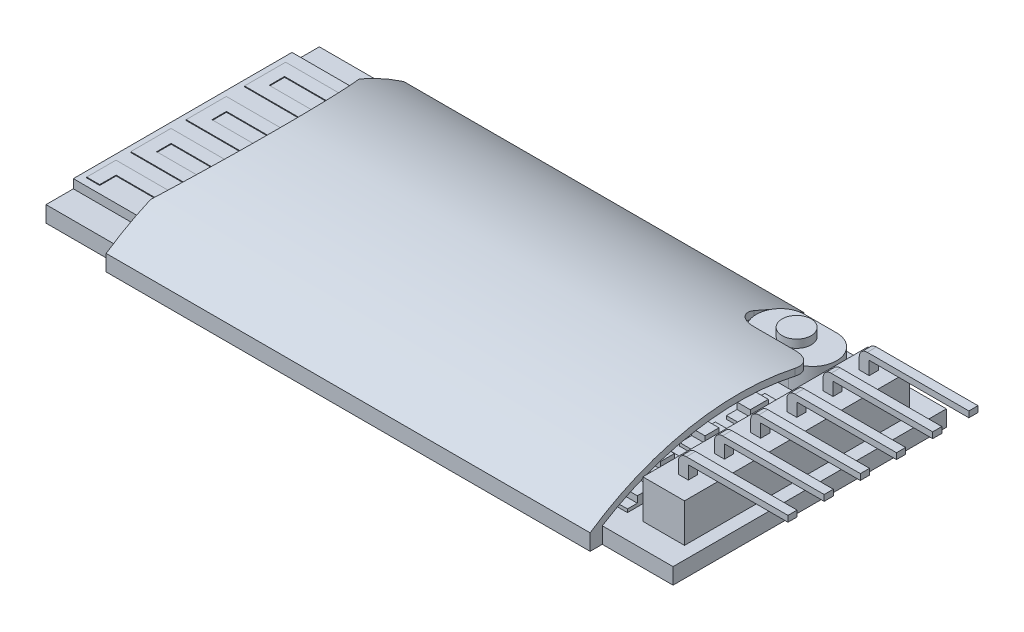
SolidWorks part; units mm, degrees
ref_plane "前视基准面" through (0, 0, 0) normal (0, 0, 1) x (1, 0, 0)
ref_plane "上视基准面" through (0, 0, 0) normal (0, 1, 0) x (1, 0, 0)
ref_plane "右视基准面" through (0, 0, 0) normal (1, 0, 0) x (0, 0, -1)
sketch "草图1" plane through (0, 0, 0) normal (0, 1, 0) x (1, 0, 0)
  line L1 (-19.5, 8.5) -> (19.5, 8.5)
  line L2 (-19.5, 8.5) -> (-19.5, -8.5)
  line L3 (-19.5, -8.5) -> (19.5, -8.5)
  line L4 (19.5, 8.5) -> (19.5, -8.5)
  line L5 (-19.5, 8.5) -> (19.5, -8.5) construction
  line L6 (-19.5, -8.5) -> (19.5, 8.5) construction
  point P0 (0, 0)
  dimension "D1" = 39
  dimension "D2" = 17
extrude "凸台-拉伸1" add sketch "草图1" along normal blind 1
sketch "草图2" plane through (0, 1, 0) normal (0, 1, 0) x (1, 0, 0)
  line L0 (-19.5, 8.5) -> (-19.5, -8.5) construction
  line L1 (-19.5, 6.8) -> (9.5, 6.8)
  line L2 (-19.5, 6.8) -> (-19.5, -6.8)
  line L3 (-19.5, -6.8) -> (9.5, -6.8)
  line L4 (9.5, 6.8) -> (9.5, -6.8)
  line L5 (-19.5, 6.8) -> (9.5, -6.8) construction
  line L6 (-19.5, -6.8) -> (9.5, 6.8) construction
  line L7 (19.5, 8.5) -> (-19.5, 8.5) construction
  line L8 (-19.5, -8.5) -> (19.5, -8.5) construction
  point P4 (-5, 0)
  dimension "D1" = 1.7
  dimension "D2" = 29
  dimension "D3" = 1.7
extrude "凸台-拉伸2" add sketch "草图2" along normal blind 0.5
sketch "草图3" plane through (0, 1.5, 0) normal (0, 1, 0) x (1, 0, 0)
  line L0 (-13.945, 4.2678) -> (-13.945, 1.5334)
  line L1 (-19.1193, 6.0235) -> (-13.945, 6.0235)
  line L2 (-19.1193, 6.0235) -> (-19.1193, 3.4678)
  line L3 (-19.1193, -6.3499) -> (-18.3103, -6.3499)
  line L5 (-19.1193, 6.0235) -> (-13.945, -6.3499) construction
  line L6 (-19.1193, -6.3499) -> (-13.945, 6.0235) construction
  line L7 (-13.945, 5.2235) -> (-18.3851, 5.2235)
  line L9 (-13.945, 4.2678) -> (-18.3851, 4.2678)
  line L10 (-18.3851, 5.2235) -> (-18.3851, 4.2678)
  line L11 (-13.945, 5.2235) -> (-18.3851, 4.2678) construction
  line L12 (-13.945, 4.2678) -> (-18.3851, 5.2235) construction
  line L13 (-19.1193, 3.4678) -> (-14.681, 3.4678)
  line L15 (-19.1193, 2.3334) -> (-14.681, 2.3334)
  line L16 (-14.681, 3.4678) -> (-14.681, 2.3334)
  line L17 (-19.1193, 3.4678) -> (-14.681, 2.3334) construction
  line L18 (-19.1193, 2.3334) -> (-14.681, 3.4678) construction
  line L19 (-13.945, 1.5334) -> (-18.3103, 1.5334)
  line L21 (-13.945, 0.6368) -> (-18.3103, 0.6368)
  line L22 (-18.3103, 1.5334) -> (-18.3103, 0.6368)
  line L23 (-13.945, 1.5334) -> (-18.3103, 0.6368) construction
  line L24 (-13.945, 0.6368) -> (-18.3103, 1.5334) construction
  line L25 (-19.1193, -0.1632) -> (-14.6759, -0.1632)
  line L27 (-19.1193, -1.1073) -> (-14.6759, -1.1073)
  line L28 (-14.6759, -0.1632) -> (-14.6759, -1.1073)
  line L29 (-19.1193, -0.1632) -> (-14.6759, -1.1073) construction
  line L30 (-19.1193, -1.1073) -> (-14.6759, -0.1632) construction
  line L31 (-13.945, -1.9073) -> (-18.3103, -1.9073)
  line L33 (-13.945, -2.809) -> (-18.3103, -2.809)
  line L34 (-18.3103, -1.9073) -> (-18.3103, -2.809)
  line L35 (-13.945, -1.9073) -> (-18.3103, -2.809) construction
  line L36 (-13.945, -2.809) -> (-18.3103, -1.9073) construction
  line L37 (-19.1193, -3.609) -> (-14.7067, -3.609)
  line L39 (-19.1193, -4.5285) -> (-14.7067, -4.5285)
  line L40 (-14.7067, -3.609) -> (-14.7067, -4.5285)
  line L41 (-19.1193, -3.609) -> (-14.7067, -4.5285) construction
  line L42 (-19.1193, -4.5285) -> (-14.7067, -3.609) construction
  line L43 (-13.945, -5.3285) -> (-18.3103, -5.3285)
  line L46 (-18.3103, -5.3285) -> (-18.3103, -6.3499)
  line L47 (-13.945, -5.3285) -> (-18.3103, -6.3499) construction
  line L48 (-13.945, -6.3499) -> (-18.3103, -5.3285) construction
  line L49 (-19.1193, 2.3334) -> (-19.1193, -0.1632)
  line L50 (-13.945, 0.6368) -> (-13.945, -1.9073)
  line L51 (-19.1193, -1.1073) -> (-19.1193, -3.609)
  line L52 (-13.945, -2.809) -> (-13.945, -5.3285)
  line L53 (-19.1193, -4.5285) -> (-19.1193, -6.3499)
  line L55 (-13.945, 6.0235) -> (-12.645, 6.0235)
  line L57 (-13.945, 5.2235) -> (-12.645, 5.2235)
  line L58 (-12.645, 6.0235) -> (-12.645, 5.2235)
  line L59 (-13.945, 6.0235) -> (-12.645, 5.2235) construction
  line L60 (-13.945, 5.2235) -> (-12.645, 6.0235) construction
  point P4 (-16.5322, -0.1632)
  point P9 (-16.1651, 4.7457)
  point P14 (-16.9002, 2.9006)
  point P19 (-16.1277, 1.0851)
  point P24 (-16.8976, -0.6352)
  point P29 (-16.1277, -2.3581)
  point P34 (-16.913, -4.0688)
  point P38 (-16.1277, -5.8392)
  point P41 (-13.295, 5.6235)
  dimension "D1" = 0.8
  dimension "D2" = 0.8
  dimension "D3" = 0.8
  dimension "D4" = 0.8
  dimension "D5" = 0.8
  dimension "D6" = 0.8
  dimension "D7" = 0.8
  dimension "D8" = 1.3
extrude "凸台-拉伸3" add sketch "草图3" along normal blind 0.1
sketch "草图4" plane through (0, 1.5, 0) normal (0, 1, 0) x (1, 0, 0)
  line L0 (-19.5, -6.8) -> (9.5, -6.8) construction
  line L1 (-19.5, 6.8) -> (-12.645, 6.8)
  line L2 (-19.5, 6.8) -> (-19.5, -6.8)
  line L3 (-19.5, -6.8) -> (-12.645, -6.8)
  line L4 (-12.645, 6.8) -> (-12.645, -6.8)
  line L5 (-19.5, 6.8) -> (-12.645, -6.8) construction
  line L6 (-19.5, -6.8) -> (-12.645, 6.8) construction
  line L7 (-12.645, 5.2235) -> (-12.645, 6.0235) construction
  point P4 (-16.0725, 0)
  dimension "D1" = 0
extrude "凸台-拉伸4" add sketch "草图4" along normal blind 0.05
sketch "草图5" plane through (0, 1.5, 0) normal (0, 1, 0) x (1, 0, 0)
  line L0 (-12.645, 0) -> (13.1235, 0) construction
  line L1 (-12.645, -6.8) -> (-12.645, 6.8) construction
  line L2 (-12.645, -6.8) -> (9.5, -6.8) construction
  line L3 (9.5, -6.8) -> (9.5, 6.8) construction
  circle A0 centre (-11.3889, -6.8) radius 0.5
  circle A1 centre (-9.2689, -6.8) radius 0.5
  circle A2 centre (-7.1489, -6.8) radius 0.5
  circle A3 centre (-5.0289, -6.8) radius 0.5
  circle A4 centre (-2.9089, -6.8) radius 0.5
  circle A5 centre (-0.7889, -6.8) radius 0.5
  circle A6 centre (1.3311, -6.8) radius 0.5
  circle A7 centre (3.4511, -6.8) radius 0.5
  circle A8 centre (5.5711, -6.8) radius 0.5
  circle A9 centre (7.6911, -6.8) radius 0.5
  circle A10 centre (7.6911, 6.8) radius 0.5
  circle A11 centre (5.5711, 6.8) radius 0.5
  circle A12 centre (3.4511, 6.8) radius 0.5
  circle A13 centre (1.3311, 6.8) radius 0.5
  circle A14 centre (-0.7889, 6.8) radius 0.5
  circle A15 centre (-2.9089, 6.8) radius 0.5
  circle A16 centre (-5.0289, 6.8) radius 0.5
  circle A17 centre (-7.1489, 6.8) radius 0.5
  circle A18 centre (-9.2689, 6.8) radius 0.5
  circle A19 centre (-11.3889, 6.8) radius 0.5
  circle A20 centre (9.5, 5.7827) radius 0.5
  circle A21 centre (9.5, 4.1327) radius 0.5
  circle A22 centre (9.5, 2.4827) radius 0.5
  circle A23 centre (9.5, 0.8327) radius 0.5
  circle A24 centre (9.5, -0.8173) radius 0.5
  circle A25 centre (9.5, -2.4673) radius 0.5
  circle A26 centre (9.5, -4.1173) radius 0.5
  circle A27 centre (9.5, -5.7673) radius 0.5
  dimension "D2" = 1
  dimension "D3" = 1
  dimension "D1" = 10
  dimension "D4" = 8
extrude "切除-拉伸1" cut sketch "草图5" against normal up to surface (0.5 mm away) up to face at (-2.5, 1, 0)
sketch "草图6" plane through (0, 1.5, 0) normal (0, 1, 0) x (1, 0, 0)
  line L0 (-11.8889, 6.8) -> (-19.5, 6.8) construction
  line L1 (-11.9389, 6.8) -> (-11.8889, 6.8)
  line L2 (-11.9389, 6.8) -> (-11.9389, 6.2)
  line L3 (-11.9389, 6.2) -> (-10.8389, 6.2)
  line L4 (-10.8389, 6.8) -> (-10.8389, 6.2)
  line L5 (-11.9389, 6.8) -> (-10.8389, 6.2) construction
  line L6 (-11.9389, 6.2) -> (-10.8389, 6.8) construction
  line L7 (-10.8889, 6.8) -> (-10.8389, 6.8)
  line L8 (-12.645, 0) -> (11.007, 0) construction
  line L9 (-12.645, -6.8) -> (-12.645, 6.8) construction
  line L10 (-9.8189, 6.8) -> (-9.7689, 6.8)
  line L11 (-9.8189, 6.8) -> (-9.8189, 6.2)
  line L12 (-9.8189, 6.2) -> (-8.7189, 6.2)
  line L13 (-8.7189, 6.8) -> (-8.7189, 6.2)
  line L14 (-8.7689, 6.8) -> (-8.7189, 6.8)
  line L15 (-7.6989, 6.8) -> (-7.6489, 6.8)
  line L16 (-7.6989, 6.8) -> (-7.6989, 6.2)
  line L17 (-7.6989, 6.2) -> (-6.5989, 6.2)
  line L18 (-6.5989, 6.8) -> (-6.5989, 6.2)
  line L19 (-6.6489, 6.8) -> (-6.5989, 6.8)
  line L20 (-5.5789, 6.8) -> (-5.5289, 6.8)
  line L21 (-5.5789, 6.8) -> (-5.5789, 6.2)
  line L22 (-5.5789, 6.2) -> (-4.4789, 6.2)
  line L23 (-4.4789, 6.8) -> (-4.4789, 6.2)
  line L24 (-4.5289, 6.8) -> (-4.4789, 6.8)
  line L25 (-3.4589, 6.8) -> (-3.4089, 6.8)
  line L26 (-3.4589, 6.8) -> (-3.4589, 6.2)
  line L27 (-3.4589, 6.2) -> (-2.3589, 6.2)
  line L28 (-2.3589, 6.8) -> (-2.3589, 6.2)
  line L29 (-2.4089, 6.8) -> (-2.3589, 6.8)
  line L30 (-1.3389, 6.8) -> (-1.2889, 6.8)
  line L31 (-1.3389, 6.8) -> (-1.3389, 6.2)
  line L32 (-1.3389, 6.2) -> (-0.2389, 6.2)
  line L33 (-0.2389, 6.8) -> (-0.2389, 6.2)
  line L34 (-0.2889, 6.8) -> (-0.2389, 6.8)
  line L35 (0.7811, 6.8) -> (0.8311, 6.8)
  line L36 (0.7811, 6.8) -> (0.7811, 6.2)
  line L37 (0.7811, 6.2) -> (1.8811, 6.2)
  line L38 (1.8811, 6.8) -> (1.8811, 6.2)
  line L39 (1.8311, 6.8) -> (1.8811, 6.8)
  line L40 (2.9011, 6.8) -> (2.9511, 6.8)
  line L41 (2.9011, 6.8) -> (2.9011, 6.2)
  line L42 (2.9011, 6.2) -> (4.0011, 6.2)
  line L43 (4.0011, 6.8) -> (4.0011, 6.2)
  line L44 (3.9511, 6.8) -> (4.0011, 6.8)
  line L45 (5.0211, 6.8) -> (5.0711, 6.8)
  line L46 (5.0211, 6.8) -> (5.0211, 6.2)
  line L47 (5.0211, 6.2) -> (6.1211, 6.2)
  line L48 (6.1211, 6.8) -> (6.1211, 6.2)
  line L49 (6.0711, 6.8) -> (6.1211, 6.8)
  line L50 (7.1411, 6.8) -> (7.1911, 6.8)
  line L51 (7.1411, 6.8) -> (7.1411, 6.2)
  line L52 (7.1411, 6.2) -> (8.2411, 6.2)
  line L53 (8.2411, 6.8) -> (8.2411, 6.2)
  line L54 (8.1911, 6.8) -> (8.2411, 6.8)
  line L55 (-9.7689, 6.8) -> (-10.8889, 6.8) construction
  line L56 (9.5, 6.2827) -> (9.5, 6.8) construction
  line L57 (9.5, 6.3327) -> (8.9, 6.3327)
  line L58 (9.5, 6.3327) -> (9.5, 6.2827)
  line L59 (9.5, 5.2327) -> (8.9, 5.2327)
  line L60 (8.9, 6.3327) -> (8.9, 5.2327)
  line L61 (9.5, 6.3327) -> (8.9, 5.2327) construction
  line L62 (9.5, 5.2327) -> (8.9, 6.3327) construction
  line L63 (9.5, 5.2827) -> (9.5, 5.2327)
  line L64 (8.9, 4.6827) -> (8.9, 3.5827)
  line L65 (9.5, 4.6827) -> (8.9, 4.6827)
  line L66 (9.5, 3.5827) -> (8.9, 3.5827)
  line L67 (8.9, 3.0327) -> (8.9, 1.9327)
  line L68 (9.5, 3.0327) -> (8.9, 3.0327)
  line L69 (9.5, 1.9327) -> (8.9, 1.9327)
  line L70 (8.9, 1.3827) -> (8.9, 0.2827)
  line L71 (9.5, 1.3827) -> (8.9, 1.3827)
  line L72 (9.5, 0.2827) -> (8.9, 0.2827)
  line L73 (8.9, -0.2673) -> (8.9, -1.3673)
  line L74 (9.5, -0.2673) -> (8.9, -0.2673)
  line L75 (9.5, -1.3673) -> (8.9, -1.3673)
  line L76 (8.9, -1.9173) -> (8.9, -3.0173)
  line L77 (9.5, -1.9173) -> (8.9, -1.9173)
  line L78 (9.5, -3.0173) -> (8.9, -3.0173)
  line L79 (8.9, -3.5673) -> (8.9, -4.6673)
  line L80 (9.5, -3.5673) -> (8.9, -3.5673)
  line L81 (9.5, -4.6673) -> (8.9, -4.6673)
  line L82 (8.9, -5.2173) -> (8.9, -6.3173)
  line L83 (9.5, -5.2173) -> (8.9, -5.2173)
  line L84 (9.5, -6.3173) -> (8.9, -6.3173)
  line L85 (9.5, 1.9827) -> (9.5, 1.9327)
  line L86 (-11.9389, -6.2) -> (-10.8389, -6.8) construction
  line L87 (-11.9389, -6.8) -> (-10.8389, -6.2) construction
  line L88 (8.1911, -6.8) -> (8.2411, -6.8)
  line L89 (8.2411, -6.8) -> (8.2411, -6.2)
  line L90 (7.1411, -6.2) -> (8.2411, -6.2)
  line L91 (7.1411, -6.8) -> (7.1411, -6.2)
  line L92 (7.1411, -6.8) -> (7.1911, -6.8)
  line L93 (6.0711, -6.8) -> (6.1211, -6.8)
  line L94 (6.1211, -6.8) -> (6.1211, -6.2)
  line L95 (5.0211, -6.2) -> (6.1211, -6.2)
  line L96 (5.0211, -6.8) -> (5.0211, -6.2)
  line L97 (5.0211, -6.8) -> (5.0711, -6.8)
  line L98 (3.9511, -6.8) -> (4.0011, -6.8)
  line L99 (4.0011, -6.8) -> (4.0011, -6.2)
  line L100 (2.9011, -6.2) -> (4.0011, -6.2)
  line L101 (2.9011, -6.8) -> (2.9011, -6.2)
  line L102 (2.9011, -6.8) -> (2.9511, -6.8)
  line L103 (1.8311, -6.8) -> (1.8811, -6.8)
  line L104 (1.8811, -6.8) -> (1.8811, -6.2)
  line L105 (0.7811, -6.2) -> (1.8811, -6.2)
  line L106 (0.7811, -6.8) -> (0.7811, -6.2)
  line L107 (0.7811, -6.8) -> (0.8311, -6.8)
  line L108 (-0.2889, -6.8) -> (-0.2389, -6.8)
  line L109 (-0.2389, -6.8) -> (-0.2389, -6.2)
  line L110 (-1.3389, -6.2) -> (-0.2389, -6.2)
  line L111 (-1.3389, -6.8) -> (-1.3389, -6.2)
  line L112 (-1.3389, -6.8) -> (-1.2889, -6.8)
  line L113 (-2.4089, -6.8) -> (-2.3589, -6.8)
  line L114 (-2.3589, -6.8) -> (-2.3589, -6.2)
  line L115 (-3.4589, -6.2) -> (-2.3589, -6.2)
  line L116 (-3.4589, -6.8) -> (-3.4589, -6.2)
  line L117 (-3.4589, -6.8) -> (-3.4089, -6.8)
  line L118 (-4.5289, -6.8) -> (-4.4789, -6.8)
  line L119 (-4.4789, -6.8) -> (-4.4789, -6.2)
  line L120 (-5.5789, -6.2) -> (-4.4789, -6.2)
  line L121 (-5.5789, -6.8) -> (-5.5789, -6.2)
  line L122 (-5.5789, -6.8) -> (-5.5289, -6.8)
  line L123 (-6.6489, -6.8) -> (-6.5989, -6.8)
  line L124 (-6.5989, -6.8) -> (-6.5989, -6.2)
  line L125 (-7.6989, -6.2) -> (-6.5989, -6.2)
  line L126 (-7.6989, -6.8) -> (-7.6989, -6.2)
  line L127 (-7.6989, -6.8) -> (-7.6489, -6.8)
  line L128 (-8.7689, -6.8) -> (-8.7189, -6.8)
  line L129 (-8.7189, -6.8) -> (-8.7189, -6.2)
  line L130 (-9.8189, -6.2) -> (-8.7189, -6.2)
  line L131 (-9.8189, -6.8) -> (-9.8189, -6.2)
  line L132 (-9.8189, -6.8) -> (-9.7689, -6.8)
  line L133 (-10.8889, -6.8) -> (-10.8389, -6.8)
  line L134 (-10.8389, -6.8) -> (-10.8389, -6.2)
  line L135 (-11.9389, -6.2) -> (-10.8389, -6.2)
  line L136 (-11.9389, -6.8) -> (-11.9389, -6.2)
  line L137 (-11.9389, -6.8) -> (-11.8889, -6.8)
  line L138 (9.5, 4.6827) -> (9.5, 4.6327)
  line L139 (9.5, 3.6327) -> (9.5, 3.5827)
  line L140 (9.5, 3.0327) -> (9.5, 2.9827)
  line L141 (9.5, 1.3827) -> (9.5, 1.3327)
  line L142 (9.5, 0.3327) -> (9.5, 0.2827)
  line L143 (9.5, -0.2673) -> (9.5, -0.3173)
  line L144 (9.5, -1.3673) -> (9.5, -1.3173)
  line L145 (9.5, -1.9173) -> (9.5, -1.9673)
  line L146 (9.5, -2.9673) -> (9.5, -3.0173)
  line L147 (9.5, -3.5673) -> (9.5, -3.6173)
  line L148 (9.5, -4.6173) -> (9.5, -4.6673)
  line L149 (9.5, -5.2173) -> (9.5, -5.2673)
  line L150 (9.5, -6.2673) -> (9.5, -6.3173)
  arc A0 (-11.8889, 6.8) -> (-10.8889, 6.8) centre (-11.3889, 6.8) ccw
  arc A1 (-9.7689, 6.8) -> (-8.7689, 6.8) centre (-9.2689, 6.8) ccw
  arc A2 (-7.6489, 6.8) -> (-6.6489, 6.8) centre (-7.1489, 6.8) ccw
  arc A3 (-5.5289, 6.8) -> (-4.5289, 6.8) centre (-5.0289, 6.8) ccw
  arc A4 (-3.4089, 6.8) -> (-2.4089, 6.8) centre (-2.9089, 6.8) ccw
  arc A5 (-1.2889, 6.8) -> (-0.2889, 6.8) centre (-0.7889, 6.8) ccw
  arc A6 (0.8311, 6.8) -> (1.8311, 6.8) centre (1.3311, 6.8) ccw
  arc A7 (2.9511, 6.8) -> (3.9511, 6.8) centre (3.4511, 6.8) ccw
  arc A8 (5.0711, 6.8) -> (6.0711, 6.8) centre (5.5711, 6.8) ccw
  arc A9 (7.1911, 6.8) -> (8.1911, 6.8) centre (7.6911, 6.8) ccw
  arc A10 (9.5, 6.2827) -> (9.5, 5.2827) centre (9.5, 5.7827) ccw
  arc A11 (9.5, 4.6327) -> (9.5, 3.6327) centre (9.5, 4.1327) ccw
  arc A12 (9.5, 2.9827) -> (9.5, 1.9827) centre (9.5, 2.4827) ccw
  arc A13 (9.5, 1.3327) -> (9.5, 0.3327) centre (9.5, 0.8327) ccw
  arc A14 (9.5, -0.3173) -> (9.5, -1.3173) centre (9.5, -0.8173) ccw
  arc A15 (9.5, -1.9673) -> (9.5, -2.9673) centre (9.5, -2.4673) ccw
  arc A16 (9.5, -3.6173) -> (9.5, -4.6173) centre (9.5, -4.1173) ccw
  arc A17 (9.5, -5.2673) -> (9.5, -6.2673) centre (9.5, -5.7673) ccw
  arc A18 (7.1911, -6.8) -> (8.1911, -6.8) centre (7.6911, -6.8) cw
  arc A19 (5.0711, -6.8) -> (6.0711, -6.8) centre (5.5711, -6.8) cw
  arc A20 (2.9511, -6.8) -> (3.9511, -6.8) centre (3.4511, -6.8) cw
  arc A21 (0.8311, -6.8) -> (1.8311, -6.8) centre (1.3311, -6.8) cw
  arc A22 (-1.2889, -6.8) -> (-0.2889, -6.8) centre (-0.7889, -6.8) cw
  arc A23 (-3.4089, -6.8) -> (-2.4089, -6.8) centre (-2.9089, -6.8) cw
  arc A24 (-5.5289, -6.8) -> (-4.5289, -6.8) centre (-5.0289, -6.8) cw
  arc A25 (-7.6489, -6.8) -> (-6.6489, -6.8) centre (-7.1489, -6.8) cw
  arc A26 (-9.7689, -6.8) -> (-8.7689, -6.8) centre (-9.2689, -6.8) cw
  arc A27 (-11.8889, -6.8) -> (-10.8889, -6.8) centre (-11.3889, -6.8) cw
  point P4 (-11.3889, 6.5)
  point P85 (9.2, 5.7827)
  point P213 (-11.3889, -6.5)
  dimension "D2" = 1.1
  dimension "D3" = 0.55
  dimension "D4" = 0.6
  dimension "D5" = 1.1
  dimension "D6" = 0.55
  dimension "D7" = 0.6
  dimension "D1" = 10
  dimension "D8" = 8
extrude "凸台-拉伸5" add sketch "草图6" along normal blind 0.05
sketch "草图9" plane through (0, 1.5, 0) normal (0, 1, 0) x (1, 0, 0)
  line L1 (-6.7387, 5.1688) -> (0.5298, 5.1688)
  line L2 (-6.7387, 5.1688) -> (-6.7387, -2.1492)
  line L3 (-6.7387, -2.1492) -> (0.5298, -2.1492)
  line L4 (0.5298, 5.1688) -> (0.5298, -2.1492)
  line L5 (-6.7387, 5.1688) -> (0.5298, -2.1492) construction
  line L6 (-6.7387, -2.1492) -> (0.5298, 5.1688) construction
  line L7 (2.1614, 5.1688) -> (8.0685, 5.1688)
  line L8 (2.1614, 5.1688) -> (2.1614, -3.3971)
  line L9 (2.1614, -3.3971) -> (8.0685, -3.3971)
  line L10 (8.0685, 5.1688) -> (8.0685, -3.3971)
  line L11 (2.1614, 5.1688) -> (8.0685, -3.3971) construction
  line L12 (2.1614, -3.3971) -> (8.0685, 5.1688) construction
  point P4 (-3.1045, 1.5098)
  point P9 (5.1149, 0.8859)
extrude "凸台-拉伸6" add sketch "草图9" along normal blind 0.8
sketch "草图10" plane through (0, 1.5, 0) normal (0, 1, 0) x (1, 0, 0)
  line L1 (-7.8532, 5.0672) -> (-7.2835, 5.0672)
  line L2 (-7.8532, 5.0672) -> (-7.8532, 3.0054)
  line L3 (-7.8532, 3.0054) -> (-7.2835, 3.0054)
  line L4 (-7.2835, 5.0672) -> (-7.2835, 3.0054)
  line L5 (-7.8532, 5.0672) -> (-7.2835, 3.0054) construction
  line L6 (-7.8532, 3.0054) -> (-7.2835, 5.0672) construction
  line L7 (-12.0311, 5.0672) -> (-11.2444, 5.0672)
  line L8 (-12.0311, 5.0672) -> (-12.0311, 3.331)
  line L9 (-12.0311, 3.331) -> (-11.2444, 3.331)
  line L10 (-11.2444, 5.0672) -> (-11.2444, 3.331)
  line L11 (-12.0311, 5.0672) -> (-11.2444, 3.331) construction
  line L12 (-12.0311, 3.331) -> (-11.2444, 5.0672) construction
  line L13 (-10.8374, 5.0672) -> (-10.1211, 5.0672)
  line L14 (-10.8374, 5.0672) -> (-10.8374, 3.331)
  line L15 (-10.8374, 3.331) -> (-10.1211, 3.331)
  line L16 (-10.1211, 5.0672) -> (-10.1211, 3.331)
  line L17 (-10.8374, 5.0672) -> (-10.1211, 3.331) construction
  line L18 (-10.8374, 3.331) -> (-10.1211, 5.0672) construction
  line L19 (-8.7485, -1.4709) -> (-7.2835, -1.4709)
  line L20 (-8.7485, -1.4709) -> (-8.7485, -2.1492)
  line L21 (-8.7485, -2.1492) -> (-7.2835, -2.1492)
  line L22 (-7.2835, -1.4709) -> (-7.2835, -2.1492)
  line L23 (-8.7485, -1.4709) -> (-7.2835, -2.1492) construction
  line L24 (-8.7485, -2.1492) -> (-7.2835, -1.4709) construction
  line L25 (-11.6377, -1.4709) -> (-10.8374, -1.4709)
  line L26 (-11.6377, -1.4709) -> (-11.6377, -3.4785)
  line L27 (-11.6377, -3.4785) -> (-10.8374, -3.4785)
  line L28 (-10.8374, -1.4709) -> (-10.8374, -3.4785)
  line L29 (-11.6377, -1.4709) -> (-10.8374, -3.4785) construction
  line L30 (-11.6377, -3.4785) -> (-10.8374, -1.4709) construction
  line L31 (-10.4792, -1.4709) -> (-9.6437, -1.4709)
  line L32 (-10.4792, -1.4709) -> (-10.4792, -3.4738)
  line L33 (-10.4792, -3.4738) -> (-9.6437, -3.4738)
  line L34 (-9.6437, -1.4709) -> (-9.6437, -3.4738)
  line L35 (-10.4792, -1.4709) -> (-9.6437, -3.4738) construction
  line L36 (-10.4792, -3.4738) -> (-9.6437, -1.4709) construction
  line L37 (-12.1459, -3.815) -> (-9.6437, -3.815)
  line L38 (-12.1459, -3.815) -> (-12.1459, -4.451)
  line L39 (-12.1459, -4.451) -> (-9.6437, -4.451)
  line L40 (-9.6437, -3.815) -> (-9.6437, -4.451)
  line L41 (-12.1459, -3.815) -> (-9.6437, -4.451) construction
  line L42 (-12.1459, -4.451) -> (-9.6437, -3.815) construction
  line L43 (-8.7485, -2.9774) -> (-7.8532, -2.9774)
  line L44 (-8.7485, -2.9774) -> (-8.7485, -5.3352)
  line L45 (-8.7485, -5.3352) -> (-7.8532, -5.3352)
  line L46 (-7.8532, -2.9774) -> (-7.8532, -5.3352)
  line L47 (-8.7485, -2.9774) -> (-7.8532, -5.3352) construction
  line L48 (-8.7485, -5.3352) -> (-7.8532, -2.9774) construction
  line L49 (-7.2835, -2.6671) -> (-6.8718, -2.6671)
  line L50 (-7.2835, -2.6671) -> (-7.2835, -3.2411)
  line L51 (-7.2835, -3.2411) -> (-6.8718, -3.2411)
  line L52 (-6.8718, -2.6671) -> (-6.8718, -3.2411)
  line L53 (-7.2835, -2.6671) -> (-6.8718, -3.2411) construction
  line L54 (-7.2835, -3.2411) -> (-6.8718, -2.6671) construction
  line L55 (-7.2835, -3.5364) -> (-6.8718, -3.5364)
  line L56 (-7.2835, -3.5364) -> (-7.2835, -4.133)
  line L57 (-7.2835, -4.133) -> (-6.8718, -4.133)
  line L58 (-6.8718, -3.5364) -> (-6.8718, -4.133)
  line L59 (-7.2835, -3.5364) -> (-6.8718, -4.133) construction
  line L60 (-7.2835, -4.133) -> (-6.8718, -3.5364) construction
  line L61 (-7.2835, -4.451) -> (-6.577, -4.451)
  line L62 (-7.2835, -4.451) -> (-7.2835, -5.1801)
  line L63 (-7.2835, -5.1801) -> (-6.577, -5.1801)
  line L64 (-6.577, -4.451) -> (-6.577, -5.1801)
  line L65 (-7.2835, -4.451) -> (-6.577, -5.1801) construction
  line L66 (-7.2835, -5.1801) -> (-6.577, -4.451) construction
  line L67 (0.8726, 4.8427) -> (1.6485, 4.8427)
  line L68 (0.8726, 4.8427) -> (0.8726, 2.6274)
  line L69 (0.8726, 2.6274) -> (1.6485, 2.6274)
  line L70 (1.6485, 4.8427) -> (1.6485, 2.6274)
  line L71 (0.8726, 4.8427) -> (1.6485, 2.6274) construction
  line L72 (0.8726, 2.6274) -> (1.6485, 4.8427) construction
  line L73 (0.8726, 2.0919) -> (1.6485, 2.0919)
  line L74 (0.8726, 2.0919) -> (0.8726, 0)
  line L75 (0.8726, 0) -> (1.6485, 0)
  line L76 (1.6485, 2.0919) -> (1.6485, 0)
  line L77 (0.8726, 2.0919) -> (1.6485, 0) construction
  line L78 (0.8726, 0) -> (1.6485, 2.0919) construction
  line L79 (0.8726, -0.4423) -> (1.6485, -0.4423)
  line L80 (0.8726, -0.4423) -> (0.8726, -2.6456)
  line L81 (0.8726, -2.6456) -> (1.6485, -2.6456)
  line L82 (1.6485, -0.4423) -> (1.6485, -2.6456)
  line L83 (0.8726, -0.4423) -> (1.6485, -2.6456) construction
  line L84 (0.8726, -2.6456) -> (1.6485, -0.4423) construction
  line L85 (3.574, -3.8347) -> (4.3685, -3.8347)
  line L86 (3.574, -3.8347) -> (3.574, -5.7088)
  line L87 (3.574, -5.7088) -> (4.3685, -5.7088)
  line L88 (4.3685, -3.8347) -> (4.3685, -5.7088)
  line L89 (3.574, -3.8347) -> (4.3685, -5.7088) construction
  line L90 (3.574, -5.7088) -> (4.3685, -3.8347) construction
  line L91 (4.9088, -3.8347) -> (5.6716, -3.8347)
  line L92 (4.9088, -3.8347) -> (4.9088, -5.7088)
  line L93 (4.9088, -5.7088) -> (5.6716, -5.7088)
  line L94 (5.6716, -3.8347) -> (5.6716, -5.7088)
  line L95 (4.9088, -3.8347) -> (5.6716, -5.7088) construction
  line L96 (4.9088, -5.7088) -> (5.6716, -3.8347) construction
  line L97 (6.1815, -3.8347) -> (7.0064, -3.8347)
  line L98 (6.1815, -3.8347) -> (6.1815, -5.7088)
  line L99 (6.1815, -5.7088) -> (7.0064, -5.7088)
  line L100 (7.0064, -3.8347) -> (7.0064, -5.7088)
  line L101 (6.1815, -3.8347) -> (7.0064, -5.7088) construction
  line L102 (6.1815, -5.7088) -> (7.0064, -3.8347) construction
  line L103 (7.5926, -3.8347) -> (8.2777, -3.8347)
  line L104 (7.5926, -3.8347) -> (7.5926, -5.7088)
  line L105 (7.5926, -5.7088) -> (8.2777, -5.7088)
  line L106 (8.2777, -3.8347) -> (8.2777, -5.7088)
  line L107 (7.5926, -3.8347) -> (8.2777, -5.7088) construction
  line L108 (7.5926, -5.7088) -> (8.2777, -3.8347) construction
  line L113 (-6.2012, -3.1428) -> (-3.3741, -5.0092) construction
  line L114 (-6.2012, -5.0092) -> (-3.3741, -3.1428) construction
  line L115 (-3.1413, -2.6671) -> (-2.6763, -2.6671)
  line L116 (-3.1413, -2.6671) -> (-3.1413, -5.3352)
  line L117 (-3.1413, -5.3352) -> (-2.6763, -5.3352)
  line L118 (-2.6763, -2.6671) -> (-2.6763, -5.3352)
  line L119 (-3.1413, -2.6671) -> (-2.6763, -5.3352) construction
  line L120 (-3.1413, -5.3352) -> (-2.6763, -2.6671) construction
  line L121 (-1.7386, -3.7335) -> (2.2851, -3.7335)
  line L122 (-1.7386, -3.7335) -> (-1.7386, -5.3772)
  line L123 (-1.7386, -5.3772) -> (2.2851, -5.3772)
  line L124 (2.2851, -3.7335) -> (2.2851, -5.3772)
  line L125 (-1.7386, -3.7335) -> (2.2851, -5.3772) construction
  line L126 (-1.7386, -5.3772) -> (2.2851, -3.7335) construction
  point P4 (-7.5683, 4.0363)
  point P9 (-11.6377, 4.1991)
  point P14 (-10.4792, 4.1991)
  point P19 (-8.016, -1.81)
  point P24 (-11.2376, -2.4747)
  point P29 (-10.0615, -2.4724)
  point P34 (-10.8948, -4.133)
  point P39 (-8.3008, -4.1563)
  point P44 (-7.0776, -2.9541)
  point P49 (-7.0776, -3.8347)
  point P54 (-6.9303, -4.8156)
  point P59 (1.2605, 3.735)
  point P64 (1.2605, 1.046)
  point P69 (1.2605, -1.544)
  point P74 (3.9713, -4.7718)
  point P79 (5.2902, -4.7718)
  point P84 (6.594, -4.7718)
  point P89 (7.9351, -4.7718)
  point P94 (-4.7876, -4.076)
  point P99 (-2.9088, -4.0012)
  point P104 (0.2732, -4.5554)
extrude "凸台-拉伸7" add sketch "草图10" along normal blind 0.2
sketch "草图11" plane through (0, 1.5, 0) normal (0, 1, 0) x (1, 0, 0)
  line L1 (-6.1682, -3.1686) -> (-3.6657, -3.1686)
  line L2 (-6.4682, -3.4686) -> (-6.4682, -4.5864)
  line L3 (-6.1682, -4.8864) -> (-3.6657, -4.8864)
  line L4 (-3.3657, -3.4686) -> (-3.3657, -4.5864)
  line L5 (-6.4682, -3.1686) -> (-3.3657, -4.8864) construction
  line L6 (-6.4682, -4.8864) -> (-3.3657, -3.1686) construction
  arc A0 (-3.6657, -3.1686) -> (-3.3657, -3.4686) centre (-3.6657, -3.4686) cw
  arc A1 (-3.6657, -4.8864) -> (-3.3657, -4.5864) centre (-3.6657, -4.5864) ccw
  arc A2 (-6.4682, -4.5864) -> (-6.1682, -4.8864) centre (-6.1682, -4.5864) ccw
  arc A3 (-6.1682, -3.1686) -> (-6.4682, -3.4686) centre (-6.1682, -3.4686) ccw
  point P4 (-4.9169, -4.0275)
  dimension "D1" = 0.3
extrude "凸台-拉伸8" add sketch "草图11" along normal blind 0.4
sketch "草图12" plane through (0, 1.9, 0) normal (0, 1, 0) x (1, 0, 0)
  line L1 (-6.158, -3.429) -> (-3.6557, -3.429)
  line L2 (-6.158, -3.429) -> (-6.158, -4.5956)
  line L3 (-6.158, -4.5956) -> (-3.6557, -4.5956)
  line L4 (-3.6557, -3.429) -> (-3.6557, -4.5956)
  line L5 (-6.158, -3.429) -> (-3.6557, -4.5956) construction
  line L6 (-6.158, -4.5956) -> (-3.6557, -3.429) construction
  point P4 (-4.9068, -4.0123)
extrude "凸台-拉伸9" add sketch "草图12" along normal blind 0.1
sketch "草图13" plane through (0, 1.7, 0) normal (0, 1, 0) x (1, 0, 0)
  line L0 (2.2851, -3.7335) -> (-1.7386, -3.7335) construction
  line L1 (-1.0021, -3.7335) -> (1.5639, -3.7335)
  line L2 (-1.0021, -3.7335) -> (-1.0021, -5.3772)
  line L3 (-1.0021, -5.3772) -> (1.5639, -5.3772)
  line L4 (1.5639, -3.7335) -> (1.5639, -5.3772)
  line L5 (-1.0021, -3.7335) -> (1.5639, -5.3772) construction
  line L6 (-1.0021, -5.3772) -> (1.5639, -3.7335) construction
  line L7 (-1.7386, -5.3772) -> (2.2851, -5.3772) construction
  point P4 (0.2809, -4.5554)
extrude "凸台-拉伸10" add sketch "草图13" along normal blind 0.6
sketch "草图14" plane through (0, 1.7, 0) normal (0, 1, 0) x (1, 0, 0)
  line L0 (-12.0311, 5.0672) -> (-12.0311, 3.331) construction
  line L1 (-12.0311, 4.6542) -> (-11.2444, 4.6542)
  line L2 (-12.0311, 4.6542) -> (-12.0311, 3.7171)
  line L3 (-12.0311, 3.7171) -> (-11.2444, 3.7171)
  line L4 (-11.2444, 4.6542) -> (-11.2444, 3.7171)
  line L5 (-12.0311, 4.6542) -> (-11.2444, 3.7171) construction
  line L6 (-12.0311, 3.7171) -> (-11.2444, 4.6542) construction
  line L7 (-11.2444, 3.331) -> (-11.2444, 5.0672) construction
  line L8 (-10.8374, 5.0672) -> (-10.8374, 3.331) construction
  line L9 (-10.8374, 4.6542) -> (-10.1211, 4.6542)
  line L10 (-10.8374, 4.6542) -> (-10.8374, 3.75)
  line L11 (-10.8374, 3.75) -> (-10.1211, 3.75)
  line L12 (-10.1211, 4.6542) -> (-10.1211, 3.75)
  line L13 (-10.8374, 4.6542) -> (-10.1211, 3.75) construction
  line L14 (-10.8374, 3.75) -> (-10.1211, 4.6542) construction
  line L15 (-10.1211, 3.331) -> (-10.1211, 5.0672) construction
  line L16 (-7.8532, 5.0672) -> (-7.8532, 3.0054) construction
  line L17 (-7.8532, 4.3583) -> (-7.2835, 4.3583)
  line L18 (-7.8532, 4.3583) -> (-7.8532, 3.8651)
  line L19 (-7.8532, 3.8651) -> (-7.2835, 3.8651)
  line L20 (-7.2835, 4.3583) -> (-7.2835, 3.8651)
  line L21 (-7.8532, 4.3583) -> (-7.2835, 3.8651) construction
  line L22 (-7.8532, 3.8651) -> (-7.2835, 4.3583) construction
  line L23 (-7.2835, 3.0054) -> (-7.2835, 5.0672) construction
  line L24 (-7.2835, -1.4709) -> (-8.7485, -1.4709) construction
  line L25 (-8.2504, -1.4709) -> (-7.8532, -1.4709)
  line L26 (-8.2504, -1.4709) -> (-8.2504, -2.1492)
  line L27 (-8.2504, -2.1492) -> (-7.8532, -2.1492)
  line L28 (-7.8532, -1.4709) -> (-7.8532, -2.1492)
  line L29 (-8.2504, -1.4709) -> (-7.8532, -2.1492) construction
  line L30 (-8.2504, -2.1492) -> (-7.8532, -1.4709) construction
  line L31 (-8.7485, -2.1492) -> (-7.2835, -2.1492) construction
  line L32 (-9.6437, -3.815) -> (-12.1459, -3.815) construction
  line L33 (-11.475, -3.815) -> (-10.289, -3.815)
  line L34 (-11.475, -3.815) -> (-11.475, -4.451)
  line L35 (-11.475, -4.451) -> (-10.289, -4.451)
  line L36 (-10.289, -3.815) -> (-10.289, -4.451)
  line L37 (-11.475, -3.815) -> (-10.289, -4.451) construction
  line L38 (-11.475, -4.451) -> (-10.289, -3.815) construction
  line L39 (-12.1459, -4.451) -> (-9.6437, -4.451) construction
  line L40 (-3.1413, -2.6671) -> (-3.1413, -5.3352) construction
  line L41 (-3.1413, -3.2729) -> (-2.6763, -3.2729)
  line L42 (-3.1413, -3.2729) -> (-3.1413, -4.6966)
  line L43 (-3.1413, -4.6966) -> (-2.6763, -4.6966)
  line L44 (-2.6763, -3.2729) -> (-2.6763, -4.6966)
  line L45 (-3.1413, -3.2729) -> (-2.6763, -4.6966) construction
  line L46 (-3.1413, -4.6966) -> (-2.6763, -3.2729) construction
  line L47 (-2.6763, -5.3352) -> (-2.6763, -2.6671) construction
  line L48 (0.8726, -0.4423) -> (0.8726, -2.6456) construction
  line L49 (0.8726, -0.9109) -> (1.6485, -0.9109)
  line L50 (0.8726, -0.9109) -> (0.8726, -2.0272)
  line L51 (0.8726, -2.0272) -> (1.6485, -2.0272)
  line L52 (1.6485, -0.9109) -> (1.6485, -2.0272)
  line L53 (0.8726, -0.9109) -> (1.6485, -2.0272) construction
  line L54 (0.8726, -2.0272) -> (1.6485, -0.9109) construction
  line L55 (1.6485, -2.6456) -> (1.6485, -0.4423) construction
  line L56 (0.8726, 2.0919) -> (0.8726, 0) construction
  line L57 (0.8726, 1.5644) -> (1.6485, 1.5644)
  line L58 (0.8726, 1.5644) -> (0.8726, 0.5937)
  line L59 (0.8726, 0.5937) -> (1.6485, 0.5937)
  line L60 (1.6485, 1.5644) -> (1.6485, 0.5937)
  line L61 (0.8726, 1.5644) -> (1.6485, 0.5937) construction
  line L62 (0.8726, 0.5937) -> (1.6485, 1.5644) construction
  line L63 (1.6485, 0) -> (1.6485, 2.0919) construction
  line L64 (0.8726, 4.8427) -> (0.8726, 2.6274) construction
  line L65 (0.8726, 4.3583) -> (1.6485, 4.3583)
  line L66 (0.8726, 4.3583) -> (0.8726, 3.2522)
  line L67 (0.8726, 3.2522) -> (1.6485, 3.2522)
  line L68 (1.6485, 4.3583) -> (1.6485, 3.2522)
  line L69 (0.8726, 4.3583) -> (1.6485, 3.2522) construction
  line L70 (0.8726, 3.2522) -> (1.6485, 4.3583) construction
  line L71 (1.6485, 2.6274) -> (1.6485, 4.8427) construction
  line L72 (3.574, -3.8347) -> (3.574, -5.7088) construction
  line L73 (3.574, -4.451) -> (4.3685, -4.451)
  line L74 (3.574, -4.451) -> (3.574, -5.1061)
  line L75 (3.574, -5.1061) -> (4.3685, -5.1061)
  line L76 (4.3685, -4.451) -> (4.3685, -5.1061)
  line L77 (3.574, -4.451) -> (4.3685, -5.1061) construction
  line L78 (3.574, -5.1061) -> (4.3685, -4.451) construction
  line L79 (4.3685, -5.7088) -> (4.3685, -3.8347) construction
  line L80 (4.9088, -3.8347) -> (4.9088, -5.7088) construction
  line L81 (4.9088, -4.451) -> (5.6716, -4.451)
  line L82 (4.9088, -4.451) -> (4.9088, -5.1061)
  line L83 (4.9088, -5.1061) -> (5.6716, -5.1061)
  line L84 (5.6716, -4.451) -> (5.6716, -5.1061)
  line L85 (4.9088, -4.451) -> (5.6716, -5.1061) construction
  line L86 (4.9088, -5.1061) -> (5.6716, -4.451) construction
  line L87 (5.6716, -5.7088) -> (5.6716, -3.8347) construction
  line L88 (6.1815, -3.8347) -> (6.1815, -5.7088) construction
  line L89 (6.1815, -4.451) -> (7.0064, -4.451)
  line L90 (6.1815, -4.451) -> (6.1815, -5.1061)
  line L91 (6.1815, -5.1061) -> (7.0064, -5.1061)
  line L92 (7.0064, -4.451) -> (7.0064, -5.1061)
  line L93 (6.1815, -4.451) -> (7.0064, -5.1061) construction
  line L94 (6.1815, -5.1061) -> (7.0064, -4.451) construction
  line L95 (7.0064, -5.7088) -> (7.0064, -3.8347) construction
  line L96 (7.5926, -3.8347) -> (7.5926, -5.7088) construction
  line L97 (7.5926, -4.451) -> (8.2777, -4.451)
  line L98 (7.5926, -4.451) -> (7.5926, -5.1061)
  line L99 (7.5926, -5.1061) -> (8.2777, -5.1061)
  line L100 (8.2777, -4.451) -> (8.2777, -5.1061)
  line L101 (7.5926, -4.451) -> (8.2777, -5.1061) construction
  line L102 (7.5926, -5.1061) -> (8.2777, -4.451) construction
  line L103 (8.2777, -5.7088) -> (8.2777, -3.8347) construction
  point P4 (-11.6377, 4.1857)
  point P13 (-10.4792, 4.2021)
  point P22 (-7.5683, 4.1117)
  point P31 (-8.0518, -1.81)
  point P40 (-10.882, -4.133)
  point P49 (-2.9088, -3.9847)
  point P58 (1.2605, -1.469)
  point P67 (1.2605, 1.079)
  point P76 (1.2605, 3.8052)
  point P85 (3.9713, -4.7786)
  point P94 (5.2902, -4.7786)
  point P103 (6.594, -4.7786)
  point P112 (7.9351, -4.7786)
extrude "凸台-拉伸11" add sketch "草图14" along normal blind 0.1
sketch "草图15" plane through (0, 1.7, 0) normal (0, 1, 0) x (1, 0, 0)
  line L0 (-11.6377, -1.4709) -> (-11.6377, -3.4785) construction
  line L1 (-11.6377, -1.9558) -> (-10.8374, -1.9558)
  line L2 (-11.6377, -1.9558) -> (-11.6377, -2.9272)
  line L3 (-11.6377, -2.9272) -> (-10.8374, -2.9272)
  line L4 (-10.8374, -1.9558) -> (-10.8374, -2.9272)
  line L5 (-11.6377, -1.9558) -> (-10.8374, -2.9272) construction
  line L6 (-11.6377, -2.9272) -> (-10.8374, -1.9558) construction
  line L7 (-10.8374, -3.4785) -> (-10.8374, -1.4709) construction
  line L8 (-10.4792, -1.4709) -> (-10.4792, -3.4738) construction
  line L9 (-10.4792, -1.9558) -> (-9.6437, -1.9558)
  line L10 (-10.4792, -1.9558) -> (-10.4792, -2.9272)
  line L11 (-10.4792, -2.9272) -> (-9.6437, -2.9272)
  line L12 (-9.6437, -1.9558) -> (-9.6437, -2.9272)
  line L13 (-10.4792, -1.9558) -> (-9.6437, -2.9272) construction
  line L14 (-10.4792, -2.9272) -> (-9.6437, -1.9558) construction
  line L15 (-9.6437, -3.4738) -> (-9.6437, -1.4709) construction
  line L16 (-8.7485, -2.9774) -> (-8.7485, -5.3352) construction
  line L17 (-8.7485, -3.6768) -> (-7.8532, -3.6768)
  line L18 (-8.7485, -3.6768) -> (-8.7485, -4.6663)
  line L19 (-8.7485, -4.6663) -> (-7.8532, -4.6663)
  line L20 (-7.8532, -3.6768) -> (-7.8532, -4.6663)
  line L21 (-8.7485, -3.6768) -> (-7.8532, -4.6663) construction
  line L22 (-8.7485, -4.6663) -> (-7.8532, -3.6768) construction
  line L23 (-7.8532, -5.3352) -> (-7.8532, -2.9774) construction
  point P4 (-11.2376, -2.4415)
  point P13 (-10.0615, -2.4415)
  point P22 (-8.3008, -4.1716)
extrude "凸台-拉伸12" add sketch "草图15" along normal blind 0.1
sketch "草图16" plane through (0, 1.5, 0) normal (0, 1, 0) x (1, 0, 0)
  line L1 (-9.1041, 2.3215) -> (-7.694, 2.3215)
  line L2 (-9.1041, 2.3215) -> (-9.1041, -0.342)
  line L3 (-9.1041, -0.342) -> (-7.694, -0.342)
  line L4 (-7.694, 2.3215) -> (-7.694, -0.342)
  line L5 (-9.1041, 2.3215) -> (-7.694, -0.342) construction
  line L6 (-9.1041, -0.342) -> (-7.694, 2.3215) construction
  point P4 (-8.3991, 0.9898)
extrude "凸台-拉伸13" add sketch "草图16" along normal blind 0.6
sketch "草图17" plane through (0, 1.5, 0) normal (0, 1, 0) x (1, 0, 0)
  line L0 (-9.1041, 2.3215) -> (-9.1041, -0.342) construction
  line L1 (-9.424, 1.9508) -> (-9.1041, 1.9508)
  line L2 (-9.424, 1.9508) -> (-9.424, 1.7565)
  line L3 (-9.424, 1.7565) -> (-9.1041, 1.7565)
  line L4 (-9.1041, 1.9508) -> (-9.1041, 1.7565)
  line L5 (-9.424, 1.9508) -> (-9.1041, 1.7565) construction
  line L6 (-9.424, 1.7565) -> (-9.1041, 1.9508) construction
  line L7 (-7.694, -0.342) -> (-7.694, 2.3215) construction
  line L8 (-9.424, 1.4219) -> (-9.1041, 1.4219)
  line L9 (-9.424, 1.4219) -> (-9.424, 1.2299)
  line L10 (-9.424, 1.2299) -> (-9.1041, 1.2299)
  line L11 (-9.1041, 1.4219) -> (-9.1041, 1.2299)
  line L12 (-9.424, 1.4219) -> (-9.1041, 1.2299) construction
  line L13 (-9.424, 1.2299) -> (-9.1041, 1.4219) construction
  line L14 (-9.424, 0.9254) -> (-9.1041, 0.9254)
  line L15 (-9.424, 0.9254) -> (-9.424, 0.6971)
  line L16 (-9.424, 0.6971) -> (-9.1041, 0.6971)
  line L17 (-9.1041, 0.9254) -> (-9.1041, 0.6971)
  line L18 (-9.424, 0.9254) -> (-9.1041, 0.6971) construction
  line L19 (-9.424, 0.6971) -> (-9.1041, 0.9254) construction
  line L20 (-9.424, 0.3857) -> (-9.1041, 0.3857)
  line L21 (-9.424, 0.3857) -> (-9.424, 0.1591)
  line L22 (-9.424, 0.1591) -> (-9.1041, 0.1591)
  line L23 (-9.1041, 0.3857) -> (-9.1041, 0.1591)
  line L24 (-9.424, 0.3857) -> (-9.1041, 0.1591) construction
  line L25 (-9.424, 0.1591) -> (-9.1041, 0.3857) construction
  line L26 (-7.694, 2.0264) -> (-7.384, 2.0264)
  line L27 (-7.694, 2.0264) -> (-7.694, 1.8537)
  line L28 (-7.694, 1.8537) -> (-7.384, 1.8537)
  line L29 (-7.384, 2.0264) -> (-7.384, 1.8537)
  line L30 (-7.694, 2.0264) -> (-7.384, 1.8537) construction
  line L31 (-7.694, 1.8537) -> (-7.384, 2.0264) construction
  line L33 (-7.694, 1.573) -> (-7.384, 1.573)
  line L34 (-7.694, 1.573) -> (-7.694, 1.3259)
  line L35 (-7.694, 1.3259) -> (-7.384, 1.3259)
  line L36 (-7.384, 1.573) -> (-7.384, 1.3259)
  line L37 (-7.694, 1.573) -> (-7.384, 1.3259) construction
  line L38 (-7.694, 1.3259) -> (-7.384, 1.573) construction
  line L39 (-7.694, 0.9254) -> (-7.384, 0.9254)
  line L40 (-7.694, 0.9254) -> (-7.694, 0.8112)
  line L41 (-7.694, 0.8112) -> (-7.384, 0.8112)
  line L42 (-7.384, 0.9254) -> (-7.384, 0.8112)
  line L43 (-7.694, 0.9254) -> (-7.384, 0.8112) construction
  line L44 (-7.694, 0.8112) -> (-7.384, 0.9254) construction
  line L45 (-7.694, 0.3857) -> (-7.384, 0.3857)
  line L46 (-7.694, 0.3857) -> (-7.694, 0.1591)
  line L47 (-7.694, 0.1591) -> (-7.384, 0.1591)
  line L48 (-7.384, 0.3857) -> (-7.384, 0.1591)
  line L49 (-7.694, 0.3857) -> (-7.384, 0.1591) construction
  line L50 (-7.694, 0.1591) -> (-7.384, 0.3857) construction
  point P4 (-9.264, 1.8537)
  point P11 (-9.264, 1.3259)
  point P16 (-9.264, 0.8112)
  point P21 (-9.264, 0.2724)
  point P26 (-7.539, 1.94)
  point P33 (-7.539, 1.4495)
  point P38 (-7.539, 0.8683)
  point P43 (-7.539, 0.2724)
extrude "凸台-拉伸14" add sketch "草图17" along normal blind 0.2
sketch "草图18" plane through (0, 1, 0) normal (0, 1, 0) x (1, 0, 0)
  line L0 (11.5, 6.1836) -> (13.5, 6.1836) construction
  line L1 (11.5, 7.6803) -> (13.5, 7.6803)
  line L2 (11.5, 4.687) -> (13.5, 4.687)
  line L3 (9.5, 6.3327) -> (9.5, 6.8) construction
  arc A0 (11.5, 7.6803) -> (11.5, 4.687) centre (11.5, 6.1836) ccw
  arc A1 (13.5, 4.687) -> (13.5, 7.6803) centre (13.5, 6.1836) ccw
  point P2 (12.5, 6.1836)
  point P7 (0, 0)
  dimension "D1" = 2
  dimension "D2" = 2
extrude "凸台-拉伸15" add sketch "草图18" along normal blind 1.5
sketch "草图19" plane through (0, 2.5, 0) normal (0, 1, 0) x (1, 0, 0)
  circle A0 centre (12.4513, 6.2382) radius 0.9029
extrude "凸台-拉伸16" add sketch "草图19" along normal blind 0.5
sketch "草图20" plane through (0, 1, 0) normal (0, 1, 0) x (1, 0, 0)
  line L1 (10.5836, 4.0799) -> (11.5014, 4.0799)
  line L2 (10.5836, 4.0799) -> (10.5836, 1.403)
  line L3 (10.5836, 1.403) -> (11.5014, 1.403)
  line L4 (11.5014, 4.0799) -> (11.5014, 1.403)
  line L5 (10.5836, 4.0799) -> (11.5014, 1.403) construction
  line L6 (10.5836, 1.403) -> (11.5014, 4.0799) construction
  line L7 (13.2239, 3.4893) -> (14.0508, 3.4893)
  line L8 (13.2239, 3.4893) -> (13.2239, 1.0971)
  line L9 (13.2239, 1.0971) -> (14.0508, 1.0971)
  line L10 (14.0508, 3.4893) -> (14.0508, 1.0971)
  line L11 (13.2239, 3.4893) -> (14.0508, 1.0971) construction
  line L12 (13.2239, 1.0971) -> (14.0508, 3.4893) construction
  line L13 (14.6117, 3.4893) -> (15.3765, 3.4893)
  line L14 (14.6117, 3.4893) -> (14.6117, 1.0971)
  line L15 (14.6117, 1.0971) -> (15.3765, 1.0971)
  line L16 (15.3765, 3.4893) -> (15.3765, 1.0971)
  line L17 (14.6117, 3.4893) -> (15.3765, 1.0971) construction
  line L18 (14.6117, 1.0971) -> (15.3765, 3.4893) construction
  line L19 (13.2239, 0.4088) -> (14.0508, 0.4088)
  line L20 (13.2239, 0.4088) -> (13.2239, -1.8093)
  line L21 (13.2239, -1.8093) -> (14.0508, -1.8093)
  line L22 (14.0508, 0.4088) -> (14.0508, -1.8093)
  line L23 (13.2239, 0.4088) -> (14.0508, -1.8093) construction
  line L24 (13.2239, -1.8093) -> (14.0508, 0.4088) construction
  line L25 (14.6117, 0.4088) -> (15.3765, 0.4088)
  line L26 (14.6117, 0.4088) -> (14.6117, -1.8093)
  line L27 (14.6117, -1.8093) -> (15.3765, -1.8093)
  line L28 (15.3765, 0.4088) -> (15.3765, -1.8093)
  line L29 (14.6117, 0.4088) -> (15.3765, -1.8093) construction
  line L30 (14.6117, -1.8093) -> (15.3765, 0.4088) construction
  line L31 (13.2239, -2.5515) -> (14.0508, -2.5515)
  line L32 (13.2239, -2.5515) -> (13.2239, -4.3077)
  line L33 (13.2239, -4.3077) -> (14.0508, -4.3077)
  line L34 (14.0508, -2.5515) -> (14.0508, -4.3077)
  line L35 (13.2239, -2.5515) -> (14.0508, -4.3077) construction
  line L36 (13.2239, -4.3077) -> (14.0508, -2.5515) construction
  line L37 (14.6117, -2.5515) -> (15.3765, -2.5515)
  line L38 (14.6117, -2.5515) -> (14.6117, -4.3077)
  line L39 (14.6117, -4.3077) -> (15.3765, -4.3077)
  line L40 (15.3765, -2.5515) -> (15.3765, -4.3077)
  line L41 (14.6117, -2.5515) -> (15.3765, -4.3077) construction
  line L42 (14.6117, -4.3077) -> (15.3765, -2.5515) construction
  line L43 (11.1955, -4.8941) -> (11.9603, -4.8941)
  line L44 (11.1955, -4.8941) -> (11.1955, -7.0101)
  line L45 (11.1955, -7.0101) -> (11.9603, -7.0101)
  line L46 (11.9603, -4.8941) -> (11.9603, -7.0101)
  line L47 (11.1955, -4.8941) -> (11.9603, -7.0101) construction
  line L48 (11.1955, -7.0101) -> (11.9603, -4.8941) construction
  line L49 (12.8056, -4.8941) -> (13.6373, -4.8941)
  line L50 (12.8056, -4.8941) -> (12.8056, -7.0101)
  line L51 (12.8056, -7.0101) -> (13.6373, -7.0101)
  line L52 (13.6373, -4.8941) -> (13.6373, -7.0101)
  line L53 (12.8056, -4.8941) -> (13.6373, -7.0101) construction
  line L54 (12.8056, -7.0101) -> (13.6373, -4.8941) construction
  line L55 (14.2803, -4.8941) -> (15.1726, -4.8941)
  line L56 (14.2803, -4.8941) -> (14.2803, -7.0101)
  line L57 (14.2803, -7.0101) -> (15.1726, -7.0101)
  line L58 (15.1726, -4.8941) -> (15.1726, -7.0101)
  line L59 (14.2803, -4.8941) -> (15.1726, -7.0101) construction
  line L60 (14.2803, -7.0101) -> (15.1726, -4.8941) construction
  line L61 (10.1193, -0.7002) -> (12.529, -0.7002)
  line L62 (10.1193, -0.7002) -> (10.1193, -1.5502)
  line L63 (10.1193, -1.5502) -> (12.529, -1.5502)
  line L64 (12.529, -0.7002) -> (12.529, -1.5502)
  line L65 (10.1193, -0.7002) -> (12.529, -1.5502) construction
  line L66 (10.1193, -1.5502) -> (12.529, -0.7002) construction
  line L67 (10.1193, -2.5515) -> (12.529, -2.5515)
  line L68 (10.1193, -2.5515) -> (10.1193, -3.4007)
  line L69 (10.1193, -3.4007) -> (12.529, -3.4007)
  line L70 (12.529, -2.5515) -> (12.529, -3.4007)
  line L71 (10.1193, -2.5515) -> (12.529, -3.4007) construction
  line L72 (10.1193, -3.4007) -> (12.529, -2.5515) construction
  point P4 (11.0425, 2.7414)
  point P9 (13.6373, 2.2932)
  point P14 (14.9941, 2.2932)
  point P19 (13.6373, -0.7002)
  point P24 (14.9941, -0.7002)
  point P29 (13.6373, -3.4296)
  point P34 (14.9941, -3.4296)
  point P39 (11.5779, -5.9521)
  point P44 (13.2215, -5.9521)
  point P49 (14.7264, -5.9521)
  point P54 (11.3242, -1.1252)
  point P59 (11.3242, -2.9761)
extrude "凸台-拉伸17" add sketch "草图20" along normal blind 0.2
sketch "草图21" plane through (0, 1.2, 0) normal (0, 1, 0) x (1, 0, 0)
  line L0 (13.2239, 0.4088) -> (13.2239, -1.8093) construction
  line L1 (13.2239, -0.1926) -> (14.0508, -0.1926)
  line L2 (13.2239, -0.1926) -> (13.2239, -1.0602)
  line L3 (13.2239, -1.0602) -> (14.0508, -1.0602)
  line L4 (14.0508, -0.1926) -> (14.0508, -1.0602)
  line L5 (13.2239, -0.1926) -> (14.0508, -1.0602) construction
  line L6 (13.2239, -1.0602) -> (14.0508, -0.1926) construction
  line L7 (14.0508, -1.8093) -> (14.0508, 0.4088) construction
  line L8 (14.6117, 0.4088) -> (14.6117, -1.8093) construction
  line L9 (14.6117, -0.1926) -> (15.3765, -0.1926)
  line L10 (14.6117, -0.1926) -> (14.6117, -1.0602)
  line L11 (14.6117, -1.0602) -> (15.3765, -1.0602)
  line L12 (15.3765, -0.1926) -> (15.3765, -1.0602)
  line L13 (14.6117, -0.1926) -> (15.3765, -1.0602) construction
  line L14 (14.6117, -1.0602) -> (15.3765, -0.1926) construction
  line L15 (15.3765, -1.8093) -> (15.3765, 0.4088) construction
  line L16 (14.6117, -2.5515) -> (14.6117, -4.3077) construction
  line L17 (14.6117, -3.2185) -> (15.3765, -3.2185)
  line L18 (14.6117, -3.2185) -> (14.6117, -3.8745)
  line L19 (14.6117, -3.8745) -> (15.3765, -3.8745)
  line L20 (15.3765, -3.2185) -> (15.3765, -3.8745)
  line L21 (14.6117, -3.2185) -> (15.3765, -3.8745) construction
  line L22 (14.6117, -3.8745) -> (15.3765, -3.2185) construction
  line L23 (15.3765, -4.3077) -> (15.3765, -2.5515) construction
  line L24 (11.1955, -4.8941) -> (11.1955, -7.0101) construction
  line L25 (11.1955, -5.4827) -> (11.9603, -5.4827)
  line L26 (11.1955, -5.4827) -> (11.1955, -6.3099)
  line L27 (11.1955, -6.3099) -> (11.9603, -6.3099)
  line L28 (11.9603, -5.4827) -> (11.9603, -6.3099)
  line L29 (11.1955, -5.4827) -> (11.9603, -6.3099) construction
  line L30 (11.1955, -6.3099) -> (11.9603, -5.4827) construction
  line L31 (11.9603, -7.0101) -> (11.9603, -4.8941) construction
  point P4 (13.6373, -0.6264)
  point P13 (14.9941, -0.6264)
  point P22 (14.9941, -3.5465)
  point P31 (11.5779, -5.8963)
extrude "凸台-拉伸18" add sketch "草图21" along normal blind 0.4
sketch "草图22" plane through (0, 1, 0) normal (0, 1, 0) x (1, 0, 0)
  line L0 (13.2239, 3.4893) -> (13.2239, 1.0971) construction
  line L1 (13.2239, 2.8756) -> (14.0508, 2.8756)
  line L2 (13.2239, 2.8756) -> (13.2239, 1.7541)
  line L3 (13.2239, 1.7541) -> (14.0508, 1.7541)
  line L4 (14.0508, 2.8756) -> (14.0508, 1.7541)
  line L5 (13.2239, 2.8756) -> (14.0508, 1.7541) construction
  line L6 (13.2239, 1.7541) -> (14.0508, 2.8756) construction
  line L7 (14.0508, 1.0971) -> (14.0508, 3.4893) construction
  line L8 (14.6117, 3.4893) -> (14.6117, 1.0971) construction
  line L9 (14.6117, 2.8756) -> (15.3765, 2.8756)
  line L10 (14.6117, 2.8756) -> (14.6117, 1.7541)
  line L11 (14.6117, 1.7541) -> (15.3765, 1.7541)
  line L12 (15.3765, 2.8756) -> (15.3765, 1.7541)
  line L13 (14.6117, 2.8756) -> (15.3765, 1.7541) construction
  line L14 (14.6117, 1.7541) -> (15.3765, 2.8756) construction
  line L15 (15.3765, 1.0971) -> (15.3765, 3.4893) construction
  line L16 (13.2239, -2.5515) -> (13.2239, -4.3077) construction
  line L17 (13.2239, -2.9646) -> (14.0508, -2.9646)
  line L18 (13.2239, -2.9646) -> (13.2239, -3.8322)
  line L19 (13.2239, -3.8322) -> (14.0508, -3.8322)
  line L20 (14.0508, -2.9646) -> (14.0508, -3.8322)
  line L21 (13.2239, -2.9646) -> (14.0508, -3.8322) construction
  line L22 (13.2239, -3.8322) -> (14.0508, -2.9646) construction
  line L23 (14.0508, -4.3077) -> (14.0508, -2.5515) construction
  line L24 (14.2803, -4.8941) -> (14.2803, -7.0101) construction
  line L25 (14.2803, -5.4615) -> (15.1726, -5.4615)
  line L26 (14.2803, -5.4615) -> (14.2803, -6.3925)
  line L27 (14.2803, -6.3925) -> (15.1726, -6.3925)
  line L28 (15.1726, -5.4615) -> (15.1726, -6.3925)
  line L29 (14.2803, -5.4615) -> (15.1726, -6.3925) construction
  line L30 (14.2803, -6.3925) -> (15.1726, -5.4615) construction
  line L31 (15.1726, -7.0101) -> (15.1726, -4.8941) construction
  line L33 (10.6422, -0.3196) -> (12.1234, -0.3196)
  line L34 (10.6422, -0.3196) -> (10.6422, -1.9701)
  line L35 (10.6422, -1.9701) -> (12.1234, -1.9701)
  line L36 (12.1234, -0.3196) -> (12.1234, -1.9701)
  line L37 (10.6422, -0.3196) -> (12.1234, -1.9701) construction
  line L38 (10.6422, -1.9701) -> (12.1234, -0.3196) construction
  line L39 (10.6422, -2.2875) -> (12.1869, -2.2875)
  line L40 (10.6422, -2.2875) -> (10.6422, -3.8322)
  line L41 (10.6422, -3.8322) -> (12.1869, -3.8322)
  line L42 (12.1869, -2.2875) -> (12.1869, -3.8322)
  line L43 (10.6422, -2.2875) -> (12.1869, -3.8322) construction
  line L44 (10.6422, -3.8322) -> (12.1869, -2.2875) construction
  circle A0 centre (10.9808, 2.8756) radius 0.951
  point P6 (13.6373, 2.3148)
  point P15 (14.9941, 2.3148)
  point P24 (13.6373, -3.3984)
  point P33 (14.7264, -5.927)
  point P42 (11.3828, -1.1448)
  point P47 (11.4146, -3.0598)
extrude "凸台-拉伸19" add sketch "草图22" along normal blind 0.6
sketch "草图23" plane through (0, 1.2, 0) normal (0, 1, 0) x (1, 0, 0)
  line L0 (12.8056, -4.8941) -> (12.8056, -7.0101) construction
  line L1 (12.8056, -5.5013) -> (13.6373, -5.5013)
  line L2 (12.8056, -5.5013) -> (12.8056, -6.3376)
  line L3 (12.8056, -6.3376) -> (13.6373, -6.3376)
  line L4 (13.6373, -5.5013) -> (13.6373, -6.3376)
  line L5 (12.8056, -5.5013) -> (13.6373, -6.3376) construction
  line L6 (12.8056, -6.3376) -> (13.6373, -5.5013) construction
  line L7 (13.6373, -7.0101) -> (13.6373, -4.8941) construction
  point P4 (13.2215, -5.9195)
extrude "凸台-拉伸20" add sketch "草图23" along normal blind 0.4
sketch "草图24" plane through (0, 1, 0) normal (0, 1, 0) x (1, 0, 0)
  line L0 (19.5, 8.5) -> (-19.5, 8.5) construction
  line L1 (16.1238, 7) -> (18.713, 7)
  line L2 (16.1238, 7) -> (16.1238, -7)
  line L3 (16.1238, -7) -> (18.713, -7)
  line L4 (18.713, 7) -> (18.713, -7)
  line L5 (16.1238, 7) -> (18.713, -7) construction
  line L6 (16.1238, -7) -> (18.713, 7) construction
  line L7 (-19.5, -8.5) -> (19.5, -8.5) construction
  point P4 (17.4184, 0)
  dimension "D1" = 1.5
  dimension "D2" = 1.5
extrude "凸台-拉伸21" add sketch "草图24" along normal blind 2.4
sketch "草图25" plane through (0, 3.4, 0) normal (0, 1, 0) x (1, 0, 0)
  line L0 (17.094, 3.8047) -> (17.7137, 3.2366) construction
  line L1 (17.094, 6.0547) -> (17.7137, 6.0547)
  line L2 (17.094, 6.0547) -> (17.094, 5.4866)
  line L3 (17.094, 5.4866) -> (17.7137, 5.4866)
  line L4 (17.7137, 6.0547) -> (17.7137, 5.4866)
  line L5 (17.094, 6.0547) -> (17.7137, 5.4866) construction
  line L6 (17.094, 5.4866) -> (17.7137, 6.0547) construction
  line L7 (17.094, 3.2366) -> (17.7137, 3.8047) construction
  line L8 (17.094, 3.8047) -> (17.094, 3.2366)
  line L9 (17.094, 3.8047) -> (17.7137, 3.8047)
  line L10 (17.7137, 3.8047) -> (17.7137, 3.2366)
  line L11 (17.094, 3.2366) -> (17.7137, 3.2366)
  line L12 (17.094, 1.5547) -> (17.7137, 0.9866) construction
  line L13 (17.094, 0.9866) -> (17.7137, 1.5547) construction
  line L14 (17.094, 1.5547) -> (17.094, 0.9866)
  line L15 (17.094, 1.5547) -> (17.7137, 1.5547)
  line L16 (17.7137, 1.5547) -> (17.7137, 0.9866)
  line L17 (17.094, 0.9866) -> (17.7137, 0.9866)
  line L18 (17.094, -0.6953) -> (17.7137, -1.2634) construction
  line L19 (17.094, -1.2634) -> (17.7137, -0.6953) construction
  line L20 (17.094, -0.6953) -> (17.094, -1.2634)
  line L21 (17.094, -0.6953) -> (17.7137, -0.6953)
  line L22 (17.7137, -0.6953) -> (17.7137, -1.2634)
  line L23 (17.094, -1.2634) -> (17.7137, -1.2634)
  line L24 (17.094, -2.9453) -> (17.7137, -3.5134) construction
  line L25 (17.094, -3.5134) -> (17.7137, -2.9453) construction
  line L26 (17.094, -2.9453) -> (17.094, -3.5134)
  line L27 (17.094, -2.9453) -> (17.7137, -2.9453)
  line L28 (17.7137, -2.9453) -> (17.7137, -3.5134)
  line L29 (17.094, -3.5134) -> (17.7137, -3.5134)
  line L30 (17.094, -5.1953) -> (17.7137, -5.7634) construction
  line L31 (17.094, -5.7634) -> (17.7137, -5.1953) construction
  line L32 (17.094, -5.1953) -> (17.094, -5.7634)
  line L33 (17.094, -5.1953) -> (17.7137, -5.1953)
  line L34 (17.7137, -5.1953) -> (17.7137, -5.7634)
  line L35 (17.094, -5.7634) -> (17.7137, -5.7634)
  point P4 (17.4039, 5.7706)
  point P11 (17.4039, 3.5206)
  point P16 (17.4039, 1.2706)
  point P21 (17.4039, -0.9794)
  point P26 (17.4039, -3.2294)
  point P31 (17.4039, -5.4794)
  dimension "D1" = 6
extrude "凸台-拉伸22" add sketch "草图25" along normal blind 1.2
sketch "草图26" plane through (17.7137, 0, 0) normal (1, 0, 0) x (0, 0, -1)
  line L0 (-5.1953, 4.6) -> (-5.1953, 3.4) construction
  line L1 (-5.7634, 4.6) -> (-5.1953, 4.6)
  line L2 (-5.7634, 4.6) -> (-5.7634, 4.2283)
  line L3 (-5.7634, 4.2283) -> (-5.1953, 4.2283)
  line L4 (-5.1953, 4.6) -> (-5.1953, 4.2283)
  line L5 (-5.7634, 4.6) -> (-5.1953, 4.2283) construction
  line L6 (-5.7634, 4.2283) -> (-5.1953, 4.6) construction
  line L7 (-2.9453, 4.6) -> (-2.9453, 3.4) construction
  line L8 (-3.5134, 4.6) -> (-2.9453, 4.6)
  line L9 (-3.5134, 4.6) -> (-3.5134, 4.2283)
  line L10 (-3.5134, 4.2283) -> (-2.9453, 4.2283)
  line L11 (-2.9453, 4.6) -> (-2.9453, 4.2283)
  line L12 (-3.5134, 4.6) -> (-2.9453, 4.2283) construction
  line L13 (-3.5134, 4.2283) -> (-2.9453, 4.6) construction
  line L14 (-0.6953, 4.6) -> (-0.6953, 3.4) construction
  line L15 (-1.2634, 4.6) -> (-0.6953, 4.6)
  line L16 (-1.2634, 4.6) -> (-1.2634, 4.2283)
  line L17 (-1.2634, 4.2283) -> (-0.6953, 4.2283)
  line L18 (-0.6953, 4.6) -> (-0.6953, 4.2283)
  line L19 (-1.2634, 4.6) -> (-0.6953, 4.2283) construction
  line L20 (-1.2634, 4.2283) -> (-0.6953, 4.6) construction
  line L21 (1.5547, 4.6) -> (1.5547, 3.4) construction
  line L22 (0.9866, 4.6) -> (1.5547, 4.6)
  line L23 (0.9866, 4.6) -> (0.9866, 4.2283)
  line L24 (0.9866, 4.2283) -> (1.5547, 4.2283)
  line L25 (1.5547, 4.6) -> (1.5547, 4.2283)
  line L26 (0.9866, 4.6) -> (1.5547, 4.2283) construction
  line L27 (0.9866, 4.2283) -> (1.5547, 4.6) construction
  line L28 (3.8047, 4.6) -> (3.8047, 3.4) construction
  line L29 (3.2366, 4.6) -> (3.8047, 4.6)
  line L30 (3.2366, 4.6) -> (3.2366, 4.2283)
  line L31 (3.2366, 4.2283) -> (3.8047, 4.2283)
  line L32 (3.8047, 4.6) -> (3.8047, 4.2283)
  line L33 (3.2366, 4.6) -> (3.8047, 4.2283) construction
  line L34 (3.2366, 4.2283) -> (3.8047, 4.6) construction
  line L35 (6.0547, 4.6) -> (6.0547, 3.4) construction
  line L36 (5.4866, 4.6) -> (6.0547, 4.6)
  line L37 (5.4866, 4.6) -> (5.4866, 4.2283)
  line L38 (5.4866, 4.2283) -> (6.0547, 4.2283)
  line L39 (6.0547, 4.6) -> (6.0547, 4.2283)
  line L40 (5.4866, 4.6) -> (6.0547, 4.2283) construction
  line L41 (5.4866, 4.2283) -> (6.0547, 4.6) construction
  point P4 (-5.4794, 4.4141)
  point P12 (-3.2294, 4.4141)
  point P20 (-0.9794, 4.4141)
  point P28 (1.2706, 4.4141)
  point P36 (3.5206, 4.4141)
  point P44 (5.7706, 4.4141)
extrude "凸台-拉伸23" add sketch "草图26" along normal blind 6.2
fillet "圆角1" radius 0.5 6 edges at (17.094, 4.6, -5.7706) (17.094, 4.6, -3.5206) (17.094, 4.6, -1.2706) (17.094, 4.6, 0.9794) (17.094, 4.6, 3.2294) (17.094, 4.6, 5.4794)
ref_plane "基准面1" through (-15, 0, 0) normal (-1, 0, 0) x (0, 0, 1)
sketch "草图27" plane through (-15, 0, 0) normal (-1, 0, 0) x (0, 0, 1)
  line L0 (0, -2.4615) -> (0, 11.5568) construction
  line L1 (-8.5, 1) -> (-8.5, 0)
  line L2 (-8.5, 1) -> (-8.5, 0) construction
  line L3 (-8.5, 0) -> (-9.2568, 0)
  line L4 (-9.2568, 0) -> (-9.2568, 1)
  line L5 (9.2568, 0) -> (9.2568, 1)
  line L6 (8.5, 0) -> (9.2568, 0)
  line L7 (8.5, 1) -> (8.5, 0)
  arc A0 (9.2568, 1) -> (-9.2568, 1) centre (0, -12.5172) ccw
  arc A1 (8.5, 1) -> (-8.5, 1) centre (0, -12.5172) ccw
extrude "凸台-拉伸24" add sketch "草图27" against normal blind 24.9
sketch "草图28" plane through (9.9, 0, 0) normal (1, 0, 0) x (0, 0, -1)
  line L0 (4.7908, 2.7148) -> (4.7908, 3.1497)
  line L6 (8.5, 1) -> (8.5, 0)
  line L7 (8.5, 0) -> (9.2568, 0)
  line L8 (9.2568, 0) -> (9.2568, 1)
  line L9 (-9.2568, 1) -> (-9.2568, 0)
  line L10 (-9.2568, 0) -> (-8.5, 0)
  line L11 (-8.5, 0) -> (-8.5, 1)
  line L15 (-9.2568, 1) -> (-9.2568, 0)
  line L16 (-9.2568, 0) -> (-8.5, 0)
  line L17 (-8.5, 0) -> (-8.5, 1)
  arc A2 (8.5, 1) -> (-8.5, 1) centre (0, -12.5172) ccw
  arc A3 (9.2568, 1) -> (-9.2568, 1) centre (0, -12.5172) ccw
  arc A4 (4.7908, 2.7148) -> (-8.5, 1) centre (0, -12.5172) ccw
  arc A5 (4.7908, 3.1497) -> (-9.2568, 1) centre (0, -12.5172) ccw
  dimension "D1" = 0
extrude "凸台-拉伸25" add sketch "草图28" along normal blind 5.2
fillet "圆角2" radius 1.35 1 edges at (9.9, 2.9322, -4.7908)
fillet "圆角3" radius 1.3 1 edges at (15.1, 2.9322, -4.7908)
sketch "草图29" plane through (0, 1.6, 0) normal (0, 1, 0) x (1, 0, 0)
  circle A0 centre (-28.2656, 0) radius 14.7693
extrude "切除-拉伸2" cut sketch "草图29" along normal blind 10.2
sketch "草图30" plane through (0, 1, 0) normal (0, 1, 0) x (1, 0, 0)
  line L1 (-12.0106, -6.2961) -> (-10.7655, -6.2961)
  line L2 (-12.0106, -6.2961) -> (-12.0106, -7.2961)
  line L3 (-12.0106, -7.2961) -> (-10.7655, -7.2961)
  line L4 (-10.7655, -6.2961) -> (-10.7655, -7.2961)
  line L5 (-12.0106, -6.2961) -> (-10.7655, -7.2961) construction
  line L6 (-12.0106, -7.2961) -> (-10.7655, -6.2961) construction
  line L7 (-9.8906, -6.2961) -> (-8.6455, -7.2961) construction
  line L8 (-9.8906, -7.2961) -> (-8.6455, -6.2961) construction
  line L9 (-9.8906, -6.2961) -> (-9.8906, -7.2961)
  line L10 (-9.8906, -6.2961) -> (-8.6455, -6.2961)
  line L11 (-8.6455, -6.2961) -> (-8.6455, -7.2961)
  line L12 (-9.8906, -7.2961) -> (-8.6455, -7.2961)
  line L13 (-7.7706, -6.2961) -> (-6.5255, -7.2961) construction
  line L14 (-7.7706, -7.2961) -> (-6.5255, -6.2961) construction
  line L15 (-7.7706, -6.2961) -> (-7.7706, -7.2961)
  line L16 (-7.7706, -6.2961) -> (-6.5255, -6.2961)
  line L17 (-6.5255, -6.2961) -> (-6.5255, -7.2961)
  line L18 (-7.7706, -7.2961) -> (-6.5255, -7.2961)
  line L19 (-5.6506, -6.2961) -> (-4.4055, -7.2961) construction
  line L20 (-5.6506, -7.2961) -> (-4.4055, -6.2961) construction
  line L21 (-5.6506, -6.2961) -> (-5.6506, -7.2961)
  line L22 (-5.6506, -6.2961) -> (-4.4055, -6.2961)
  line L23 (-4.4055, -6.2961) -> (-4.4055, -7.2961)
  line L24 (-5.6506, -7.2961) -> (-4.4055, -7.2961)
  line L25 (-3.5306, -6.2961) -> (-2.2855, -7.2961) construction
  line L26 (-3.5306, -7.2961) -> (-2.2855, -6.2961) construction
  line L27 (-3.5306, -6.2961) -> (-3.5306, -7.2961)
  line L28 (-3.5306, -6.2961) -> (-2.2855, -6.2961)
  line L29 (-2.2855, -6.2961) -> (-2.2855, -7.2961)
  line L30 (-3.5306, -7.2961) -> (-2.2855, -7.2961)
  line L31 (-1.4106, -6.2961) -> (-0.1655, -7.2961) construction
  line L32 (-1.4106, -7.2961) -> (-0.1655, -6.2961) construction
  line L33 (-1.4106, -6.2961) -> (-1.4106, -7.2961)
  line L34 (-1.4106, -6.2961) -> (-0.1655, -6.2961)
  line L35 (-0.1655, -6.2961) -> (-0.1655, -7.2961)
  line L36 (-1.4106, -7.2961) -> (-0.1655, -7.2961)
  line L37 (0.7094, -6.2961) -> (1.9545, -7.2961) construction
  line L38 (0.7094, -7.2961) -> (1.9545, -6.2961) construction
  line L39 (0.7094, -6.2961) -> (0.7094, -7.2961)
  line L40 (0.7094, -6.2961) -> (1.9545, -6.2961)
  line L41 (1.9545, -6.2961) -> (1.9545, -7.2961)
  line L42 (0.7094, -7.2961) -> (1.9545, -7.2961)
  line L43 (2.8294, -6.2961) -> (4.0745, -7.2961) construction
  line L44 (2.8294, -7.2961) -> (4.0745, -6.2961) construction
  line L45 (2.8294, -6.2961) -> (2.8294, -7.2961)
  line L46 (2.8294, -6.2961) -> (4.0745, -6.2961)
  line L47 (4.0745, -6.2961) -> (4.0745, -7.2961)
  line L48 (2.8294, -7.2961) -> (4.0745, -7.2961)
  line L49 (4.9494, -6.2961) -> (6.1945, -7.2961) construction
  line L50 (4.9494, -7.2961) -> (6.1945, -6.2961) construction
  line L51 (4.9494, -6.2961) -> (4.9494, -7.2961)
  line L52 (4.9494, -6.2961) -> (6.1945, -6.2961)
  line L53 (6.1945, -6.2961) -> (6.1945, -7.2961)
  line L54 (4.9494, -7.2961) -> (6.1945, -7.2961)
  line L55 (7.0694, -6.2961) -> (8.3145, -7.2961) construction
  line L56 (7.0694, -7.2961) -> (8.3145, -6.2961) construction
  line L57 (7.0694, -6.2961) -> (7.0694, -7.2961)
  line L58 (7.0694, -6.2961) -> (8.3145, -6.2961)
  line L59 (8.3145, -6.2961) -> (8.3145, -7.2961)
  line L60 (7.0694, -7.2961) -> (8.3145, -7.2961)
  line L61 (-12.645, 0) -> (10.1286, 0) construction
  line L62 (-12.645, -6.8) -> (-12.645, 5.2235) construction
  line L63 (8.5686, -3.5477) -> (8.5686, -4.6634)
  line L64 (9.8734, -5.1977) -> (8.5686, -5.1977)
  line L65 (9.8734, -5.1977) -> (9.8734, -6.3134)
  line L66 (9.8734, -6.3134) -> (8.5686, -6.3134)
  line L67 (8.5686, -5.1977) -> (8.5686, -6.3134)
  line L68 (9.8734, -5.1977) -> (8.5686, -6.3134) construction
  line L69 (9.8734, -6.3134) -> (8.5686, -5.1977) construction
  line L70 (9.8734, -3.5477) -> (8.5686, -3.5477)
  line L71 (9.8734, -4.6634) -> (8.5686, -4.6634)
  line L72 (9.8734, -3.5477) -> (9.8734, -4.6634)
  line L73 (8.5686, -1.8977) -> (8.5686, -3.0134)
  line L74 (9.8734, -1.8977) -> (8.5686, -1.8977)
  line L75 (9.8734, -3.0134) -> (8.5686, -3.0134)
  line L76 (9.8734, -1.8977) -> (9.8734, -3.0134)
  line L77 (8.5686, -0.2477) -> (8.5686, -1.3634)
  line L78 (9.8734, -0.2477) -> (8.5686, -0.2477)
  line L79 (9.8734, -1.3634) -> (8.5686, -1.3634)
  line L80 (9.8734, -0.2477) -> (9.8734, -1.3634)
  line L81 (8.5686, 1.4023) -> (8.5686, 0.2866)
  line L82 (9.8734, 1.4023) -> (8.5686, 1.4023)
  line L83 (9.8734, 0.2866) -> (8.5686, 0.2866)
  line L84 (9.8734, 1.4023) -> (9.8734, 0.2866)
  line L85 (8.5686, 3.0523) -> (8.5686, 1.9366)
  line L86 (9.8734, 3.0523) -> (8.5686, 3.0523)
  line L87 (9.8734, 1.9366) -> (8.5686, 1.9366)
  line L88 (9.8734, 3.0523) -> (9.8734, 1.9366)
  line L89 (8.5686, 4.7023) -> (8.5686, 3.5866)
  line L90 (9.8734, 4.7023) -> (8.5686, 4.7023)
  line L91 (9.8734, 3.5866) -> (8.5686, 3.5866)
  line L92 (9.8734, 4.7023) -> (9.8734, 3.5866)
  line L93 (8.5686, 6.3523) -> (8.5686, 5.2366)
  line L94 (9.8734, 6.3523) -> (8.5686, 6.3523)
  line L95 (9.8734, 5.2366) -> (8.5686, 5.2366)
  line L96 (9.8734, 6.3523) -> (9.8734, 5.2366)
  line L98 (7.0694, 7.2961) -> (8.3145, 6.2961) construction
  line L99 (7.0694, 6.2961) -> (8.3145, 7.2961) construction
  line L100 (4.9494, 7.2961) -> (6.1945, 6.2961) construction
  line L101 (4.9494, 6.2961) -> (6.1945, 7.2961) construction
  line L102 (2.8294, 7.2961) -> (4.0745, 6.2961) construction
  line L103 (2.8294, 6.2961) -> (4.0745, 7.2961) construction
  line L104 (0.7094, 7.2961) -> (1.9545, 6.2961) construction
  line L105 (0.7094, 6.2961) -> (1.9545, 7.2961) construction
  line L106 (-1.4106, 7.2961) -> (-0.1655, 6.2961) construction
  line L107 (-1.4106, 6.2961) -> (-0.1655, 7.2961) construction
  line L108 (-3.5306, 7.2961) -> (-2.2855, 6.2961) construction
  line L109 (-3.5306, 6.2961) -> (-2.2855, 7.2961) construction
  line L110 (-5.6506, 7.2961) -> (-4.4055, 6.2961) construction
  line L111 (-5.6506, 6.2961) -> (-4.4055, 7.2961) construction
  line L112 (-7.7706, 7.2961) -> (-6.5255, 6.2961) construction
  line L113 (-7.7706, 6.2961) -> (-6.5255, 7.2961) construction
  line L114 (-9.8906, 7.2961) -> (-8.6455, 6.2961) construction
  line L115 (-9.8906, 6.2961) -> (-8.6455, 7.2961) construction
  line L116 (-12.0106, 7.2961) -> (-10.7655, 6.2961) construction
  line L117 (-12.0106, 6.2961) -> (-10.7655, 7.2961) construction
  line L118 (7.0694, 7.2961) -> (8.3145, 7.2961)
  line L119 (8.3145, 6.2961) -> (8.3145, 7.2961)
  line L120 (7.0694, 6.2961) -> (8.3145, 6.2961)
  line L121 (7.0694, 6.2961) -> (7.0694, 7.2961)
  line L122 (4.9494, 7.2961) -> (6.1945, 7.2961)
  line L123 (6.1945, 6.2961) -> (6.1945, 7.2961)
  line L124 (4.9494, 6.2961) -> (6.1945, 6.2961)
  line L125 (4.9494, 6.2961) -> (4.9494, 7.2961)
  line L126 (2.8294, 7.2961) -> (4.0745, 7.2961)
  line L127 (4.0745, 6.2961) -> (4.0745, 7.2961)
  line L128 (2.8294, 6.2961) -> (4.0745, 6.2961)
  line L129 (2.8294, 6.2961) -> (2.8294, 7.2961)
  line L130 (0.7094, 7.2961) -> (1.9545, 7.2961)
  line L131 (1.9545, 6.2961) -> (1.9545, 7.2961)
  line L132 (0.7094, 6.2961) -> (1.9545, 6.2961)
  line L133 (0.7094, 6.2961) -> (0.7094, 7.2961)
  line L134 (-1.4106, 7.2961) -> (-0.1655, 7.2961)
  line L135 (-0.1655, 6.2961) -> (-0.1655, 7.2961)
  line L136 (-1.4106, 6.2961) -> (-0.1655, 6.2961)
  line L137 (-1.4106, 6.2961) -> (-1.4106, 7.2961)
  line L138 (-3.5306, 7.2961) -> (-2.2855, 7.2961)
  line L139 (-2.2855, 6.2961) -> (-2.2855, 7.2961)
  line L140 (-3.5306, 6.2961) -> (-2.2855, 6.2961)
  line L141 (-3.5306, 6.2961) -> (-3.5306, 7.2961)
  line L142 (-5.6506, 7.2961) -> (-4.4055, 7.2961)
  line L143 (-4.4055, 6.2961) -> (-4.4055, 7.2961)
  line L144 (-5.6506, 6.2961) -> (-4.4055, 6.2961)
  line L145 (-5.6506, 6.2961) -> (-5.6506, 7.2961)
  line L146 (-7.7706, 7.2961) -> (-6.5255, 7.2961)
  line L147 (-6.5255, 6.2961) -> (-6.5255, 7.2961)
  line L148 (-7.7706, 6.2961) -> (-6.5255, 6.2961)
  line L149 (-7.7706, 6.2961) -> (-7.7706, 7.2961)
  line L150 (-9.8906, 7.2961) -> (-8.6455, 7.2961)
  line L151 (-8.6455, 6.2961) -> (-8.6455, 7.2961)
  line L152 (-9.8906, 6.2961) -> (-8.6455, 6.2961)
  line L153 (-9.8906, 6.2961) -> (-9.8906, 7.2961)
  line L154 (-10.7655, 6.2961) -> (-10.7655, 7.2961)
  line L155 (-12.0106, 7.2961) -> (-10.7655, 7.2961)
  line L156 (-12.0106, 6.2961) -> (-12.0106, 7.2961)
  line L157 (-12.0106, 6.2961) -> (-10.7655, 6.2961)
  point P4 (-11.3881, -6.7961)
  point P13 (-9.2681, -6.7961)
  point P18 (-7.1481, -6.7961)
  point P23 (-5.0281, -6.7961)
  point P28 (-2.9081, -6.7961)
  point P33 (-0.7881, -6.7961)
  point P38 (1.3319, -6.7961)
  point P43 (3.4519, -6.7961)
  point P48 (5.5719, -6.7961)
  point P53 (7.6919, -6.7961)
  point P61 (9.221, -5.7556)
  point P131 (7.6919, 6.7961)
  point P132 (5.5719, 6.7961)
  point P133 (3.4519, 6.7961)
  point P134 (1.3319, 6.7961)
  point P135 (-0.7881, 6.7961)
  point P136 (-2.9081, 6.7961)
  point P137 (-5.0281, 6.7961)
  point P138 (-7.1481, 6.7961)
  point P139 (-9.2681, 6.7961)
  point P140 (-11.3881, 6.7961)
  dimension "D2" = 1
  dimension "D1" = 10
  dimension "D3" = 8
extrude "凸台-拉伸26" add sketch "草图30" along normal blind 0.1
sketch "草图31" plane through (0, 2.3, 0) normal (0, 1, 0) x (1, 0, 0)
  line L0 (1.5639, -3.7335) -> (-1.0021, -3.7335) construction
  line L1 (-0.4332, -3.7335) -> (0.9584, -3.7335)
  line L2 (-0.4332, -3.7335) -> (-0.4332, -5.3772)
  line L3 (-0.4332, -5.3772) -> (0.9584, -5.3772)
  line L4 (0.9584, -3.7335) -> (0.9584, -5.3772)
  line L5 (-0.4332, -3.7335) -> (0.9584, -5.3772) construction
  line L6 (-0.4332, -5.3772) -> (0.9584, -3.7335) construction
  line L7 (-1.0021, -5.3772) -> (1.5639, -5.3772) construction
  point P4 (0.2626, -4.5554)
extrude "凸台-拉伸27" add sketch "草图31" along normal blind 0.1
